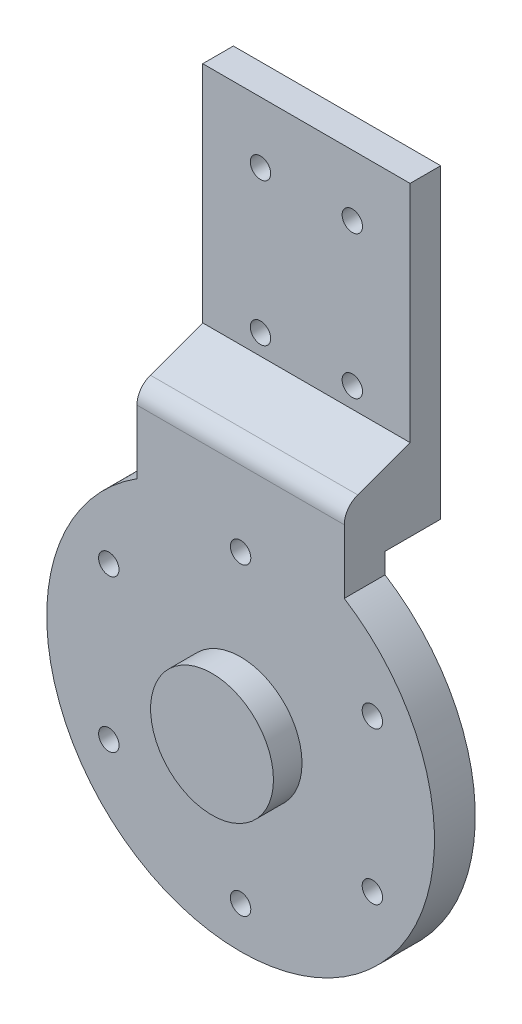
SolidWorks part; units mm, degrees
ref_plane "Front Plane" through (0, 0, 0) normal (0, 0, 1) x (1, 0, 0)
ref_plane "Top Plane" through (0, 0, 0) normal (0, 1, 0) x (1, 0, 0)
ref_plane "Right Plane" through (0, 0, 0) normal (1, 0, 0) x (0, 0, -1)
sketch "Sketch1" plane through (0, 0, 0) normal (0, 0, 1) x (1, 0, 0)
  line L0 (-25.4, 40.1384) -> (-25.4, 120.1384)
  line L1 (-25.4, 120.1384) -> (25.4, 120.1384)
  line L2 (25.4, 120.1384) -> (25.4, 40.1384)
  line L4 (-11.25, 105.1384) -> (11.25, 105.1384) construction
  line L5 (-11.25, 105.1384) -> (-11.25, 70.1384) construction
  line L6 (-11.25, 70.1384) -> (11.25, 70.1384) construction
  line L7 (11.25, 105.1384) -> (11.25, 70.1384) construction
  line L9 (-25.4, 45.1384) -> (25.4, 45.1384)
  line L10 (-25.4, 55.1384) -> (25.4, 55.1384)
  circle A2 centre (-11.25, 105.1384) radius 2.5
  circle A3 centre (11.25, 105.1384) radius 2.5
  circle A4 centre (11.25, 70.1384) radius 2.5
  circle A5 centre (-11.25, 70.1384) radius 2.5
  arc A6 (-25.4, 40.1384) -> (25.4, 40.1384) centre (0, 0) ccw
  circle A8 centre (0, 0) radius 37.28 construction
  circle A9 centre (0, 37.28) radius 2.5
  circle A10 centre (32.2854, 18.64) radius 2.5
  circle A11 centre (32.2854, -18.64) radius 2.5
  circle A12 centre (0, -37.28) radius 2.5
  circle A13 centre (-32.2854, -18.64) radius 2.5
  circle A14 centre (-32.2854, 18.64) radius 2.5
  point P13 (0, 70.1384)
  point P32 (0, 0)
  point P40 (0, 120.1384)
  dimension "D1" = 95
  dimension "D4" = 5
  dimension "D8" = 74.56
  dimension "D9" = 5
  dimension "D2" = 50.8
  dimension "D3" = 5
  dimension "D5" = 35
  dimension "D6" = 15
  dimension "D7" = 22.5
  dimension "D11" = 25
  dimension "D12" = 10
  dimension "D10" = 6
extrude "5" add sketch "Sketch1" along normal blind 7.5 contours L0 L9 L2 L1 A5 A4 A3 A2 region at (0, 87.6384, 0)
extrude "Boss-Extrude1" add sketch "Sketch1<3>" along normal blind 13.625 contours L10 L0 L9 L2 region at (0, 50.1384, 0)
sketch "Sketch1<3>" plane through (0, 0, 0) normal (0, 0, 1) x (1, 0, 0) same geometry as "Sketch1"
extrude "Boss-Extrude2" add sketch "Sketch1<4>" along normal blind 10 from surface contours A6 L2 L9 L0 A14 A13 A12 A11 A10 A9 | L10 L0 L9 L2 region at (0, -0.0136, 0) region at (0, 50.1384, 0) starting at face at (0, 50.1384, 13.625)
sketch "Sketch1<4>" plane through (0, 0, 0) normal (0, 0, 1) x (1, 0, 0) same geometry as "Sketch1"
chamfer "Chamfer1" distance 10 angle 70 1 edges at (0, 55.1384, 7.5) first distance on face at (-8.75, 70.1384, 7.5)
fillet "Fillet1" radius 5 1 edges at (0, 59.2694, 23.625)
sketch "Sketch2" plane through (0, 0, 23.625) normal (0, 0, 1) x (1, 0, 0)
  circle A0 centre (0, 0) radius 15.05
  dimension "D1" = 30.1
extrude "Boss-Extrude3" add sketch "Sketch2" along normal blind 7
